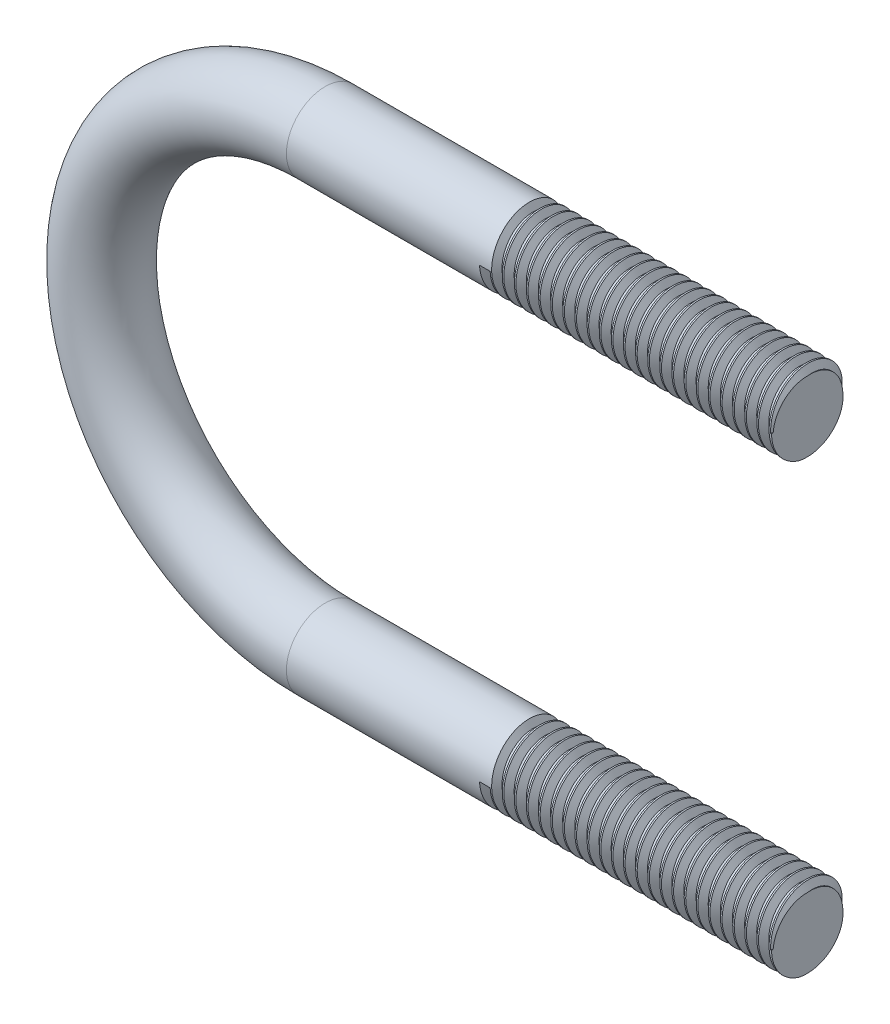
SolidWorks part; units mm, degrees
material "AISI 304"
ref_plane "Plano frontal" through (0, 0, 0) normal (0, 0, 1) x (1, 0, 0)
ref_plane "Plano superior" through (0, 0, 0) normal (0, 1, 0) x (1, 0, 0)
ref_plane "Plano direito" through (0, 0, 0) normal (1, 0, 0) x (0, 0, -1)
sketch "Esboço1" plane through (0, 0, 0) normal (0, 0, 1) x (1, 0, 0)
  circle A0 centre (0, 0) radius 19.05
  dimension "D1" = 38.1
sketch "Esboço2" plane through (0, 0, 0) normal (0, 0, 1) x (1, 0, 0)
  line L0 (0, 23.05) -> (50, 23.05)
  line L1 (0, -23.05) -> (50, -23.05)
  line L4 (0, 23.05) -> (0, -23.05) construction
  arc A0 (0, -23.05) -> (0, 23.05) centre (0, 0) cw
  dimension "D3" = 23.05
  dimension "D4" = 46.1
  dimension "D1" = 50
  dimension "D2" = 50
ref_plane "Plano1" through (50, 23.05, 0) normal (-1, 0, 0) x (0, 0, 1)
sketch "Esboço4" plane through (50, 23.05, 0) normal (-1, 0, 0) x (0, 0, 1)
  circle A0 centre (0, 0) radius 4
  dimension "D1" = 8
sweep "Varredura1" add profiles "Esboço4" path "Esboço2"
thread "Rosca1" pitch 1.25 method cut profile "Perfil da rosca1" start angle 0, offset 1, length 30, pitch 1.25, diameter 8
ref_plane "Plano2" through (51, 23.05, 4) normal (0, -1, 0) x (0, 0, 1)
sketch "Perfil da rosca1" plane through (51, 23.05, 4) normal (0, -1, 0) x (0, 0, 1)
  line L0 (0, 0) -> (0, 1.25) construction
  line L11 (0, 0) -> (0, 1.0937)
  line L12 (0, 1.0937) -> (-0.6766, 0.7031)
  line L13 (-0.6766, 0.7031) -> (-0.6766, 0.3906)
  line L15 (-0.6766, 0.3906) -> (0, 0)
  line L17 (-0.6766, 0.5469) -> (0, 0.5469) construction
  point P2 (0, 0)
  dimension "Pitch" = 1.25
  dimension "Profile_Angle" = 60
  dimension "Profile_Land" = 0.3125
  dimension "Profile_Height" = 0.6766
thread "Rosca2" pitch 1.25 method cut profile "Perfil da rosca2" start angle 0, offset 1, length 30, pitch 1.25, diameter 8
ref_plane "Plano3" through (51, -23.05, 4) normal (0, -1, 0) x (0, 0, 1)
sketch "Perfil da rosca2" plane through (51, -23.05, 4) normal (0, -1, 0) x (0, 0, 1)
  line L0 (0, 0) -> (0, 1.25) construction
  line L11 (0, 0) -> (0, 1.0937)
  line L12 (0, 1.0937) -> (-0.6766, 0.7031)
  line L13 (-0.6766, 0.7031) -> (-0.6766, 0.3906)
  line L15 (-0.6766, 0.3906) -> (0, 0)
  line L17 (-0.6766, 0.5469) -> (0, 0.5469) construction
  point P2 (0, 0)
  dimension "Pitch" = 1.25
  dimension "Profile_Angle" = 60
  dimension "Profile_Land" = 0.3125
  dimension "Profile_Height" = 0.6766
